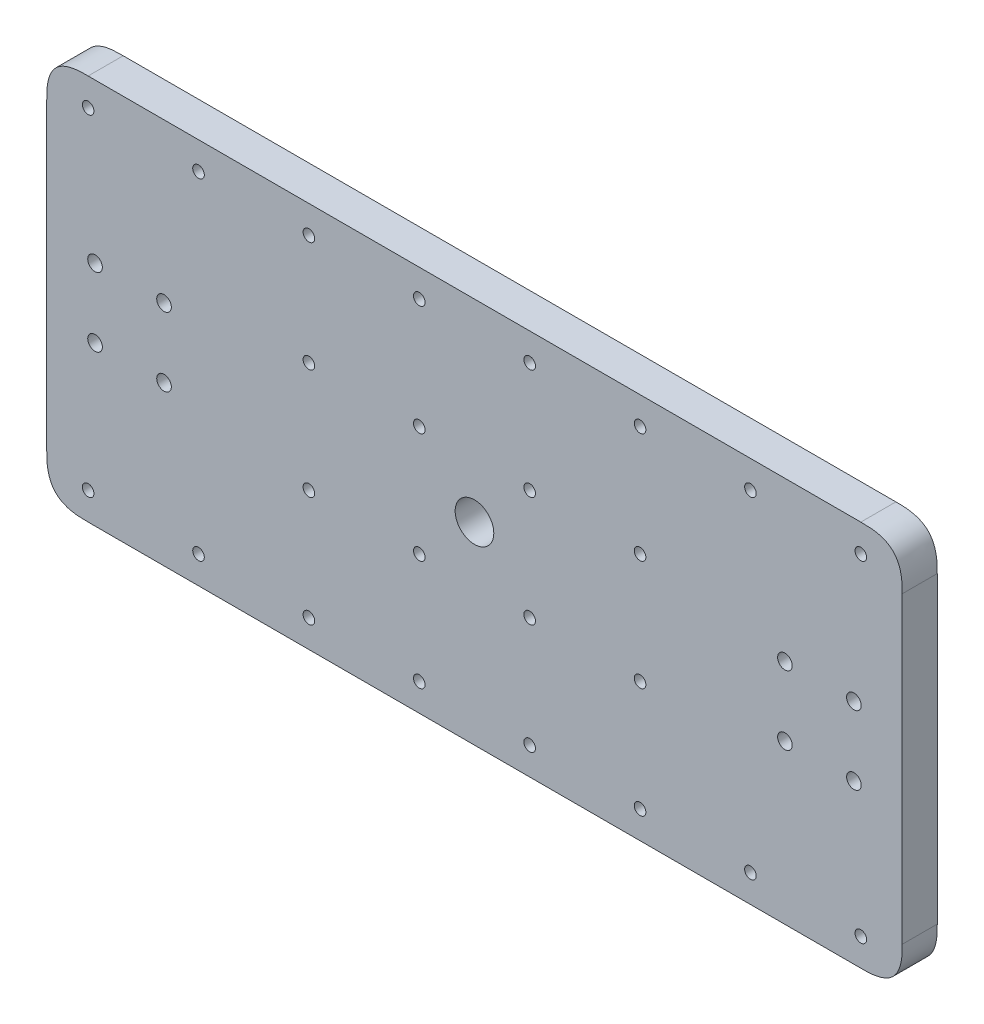
SolidWorks part; units mm, degrees
ref_plane "Front Plane" through (0, 0, 0) normal (0, 0, 1) x (1, 0, 0)
ref_plane "Top Plane" through (0, 0, 0) normal (0, 1, 0) x (1, 0, 0)
ref_plane "Right Plane" through (0, 0, 0) normal (1, 0, 0) x (0, 0, -1)
sketch "Sketch1" plane through (0, 0, 0) normal (0, 0, 1) x (1, 0, 0)
  line L1 (-155, 70) -> (155, 70)
  line L2 (-155, 70) -> (-155, -70)
  line L3 (-155, -70) -> (155, -70)
  line L4 (155, 70) -> (155, -70)
  line L5 (-155, 70) -> (155, -70) construction
  line L6 (-155, -70) -> (155, 70) construction
  point P0 (0, 0)
  dimension "D1" = 310
  dimension "D2" = 140
extrude "Boss-Extrude1" add sketch "Sketch1" along normal blind 12.7
sketch "Sketch5" plane through (0, 0, 12.7) normal (0, 0, 1) x (1, 0, 0)
  line L1 (-140, 60) -> (140, 60) construction
  line L2 (-140, 60) -> (-140, -60) construction
  line L3 (-140, -60) -> (140, -60) construction
  line L4 (140, 60) -> (140, -60) construction
  line L8 (-140, 60) -> (140, -60) construction
  point P0 (-140, 60)
  point P14 (-140, 60)
  dimension "D1" = 280
  dimension "D2" = 120
hole_wizard "Tap Drill for M5x0.8 Tap1" positions "Sketch5" profile "Sketch6" hole size "M5x0.8" standard "ANSI Metric" end condition up to next
sketch "Sketch6" plane through (-140, 60, 12.7) normal (1, 0, 0) x (0, -1, 0)
  line L0 (0, 0) -> (0, 12.7)
  line L1 (0, 12.7) -> (2.1, 12.7)
  line L2 (2.1, 12.7) -> (2.1, 0)
  line L5 (2.1, 0) -> (0, 0)
  line L11 (0, -6.35) -> (0, 107.95) construction
  dimension "Thru Hole Dia." = 4.2
  dimension "Thru Hole Depth" = 12.7
pattern_linear "LPattern1" count 8 spacing 40 along (1, 0, 0) count 4 spacing 40 along (0, -1, 0) skipping (0, 1), (0, 2), (1, 1), (1, 2), (6, 1), (6, 2), (7, 1), (7, 2) of "Tap Drill for M5x0.8 Tap1"
fillet "Fillet1" radius 15 4 edges at (155, -70, 6.35) (155, 70, 6.35) (-155, 70, 6.35) (-155, -70, 6.35) curvature continuous yes
sketch "Sketch10" plane through (0, 0, 0) normal (0, 0, -1) x (-1, 0, 0)
  point P0 (137.5, -12.5)
  point P3 (137.5, 12.5)
  point P6 (112.5, 12.5)
  point P9 (112.5, -12.5)
  point P12 (-112.5, -12.5)
  point P15 (-137.5, -12.5)
  point P18 (-112.5, 12.5)
  point P21 (-137.5, 12.5)
hole_wizard "M5 Clearance Hole1" positions "Sketch10" profile "Sketch9" hole size "M5" standard "ANSI Metric"
sketch "Sketch9" plane through (-137.5, -12.5, 0) normal (1, 0, 0) x (0, 1, 0)
  line L0 (0, 0) -> (0, 14.2923)
  line L1 (0, 14.2923) -> (2.65, 12.7)
  line L2 (2.65, 12.7) -> (2.65, 0)
  line L5 (2.65, 0) -> (0, 0)
  line L10 (0, 14.2923) -> (-2.65, 12.7) construction
  line L11 (0, -6.35) -> (0, 107.95) construction
  dimension "Hole Dia." = 5.3
  dimension "Hole Depth" = 12.7
  dimension "Drill Angle" = 118
sketch "Sketch11" plane through (0, 0, 12.7) normal (0, 0, 1) x (1, 0, 0)
  line L0 (0, 70) -> (0, -70) construction
  line L1 (140, 70) -> (-140, 70) construction
  line L2 (-140, -70) -> (140, -70) construction
  point P6 (0, 0)
sketch "Sketch14" plane through (0, 0, 12.7) normal (0, 0, 1) x (1, 0, 0)
  point P0 (0, 0)
hole_wizard "Tap Drill for M16x2.0 Tap1" positions "Sketch14" profile "Sketch13" hole size "M16x2.0" standard "ANSI Metric" end condition through all
sketch "Sketch13" plane through (0, 0, 12.7) normal (1, 0, 0) x (0, -1, 0)
  line L0 (0, 0) -> (0, 12.75)
  line L1 (0, 12.75) -> (7, 12.75)
  line L2 (7, 12.75) -> (7, 0)
  line L5 (7, 0) -> (0, 0)
  line L11 (0, -6.35) -> (0, 107.95) construction
  dimension "Thru Hole Dia." = 14
  dimension "Thru Hole Depth" = 12.75
